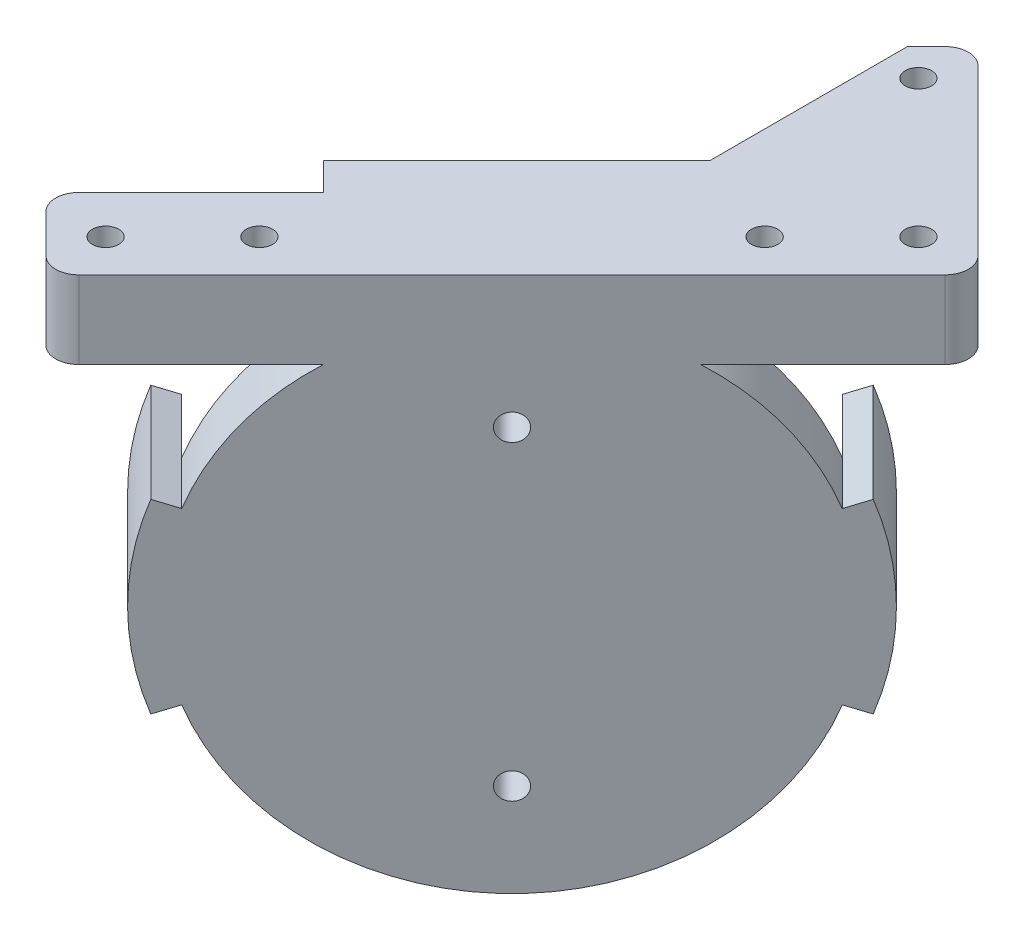
SolidWorks part; units mm, degrees
material "Zoltek Panex 33"
ref_plane "前视基准面" through (0, 0, 0) normal (0, 0, 1) x (1, 0, 0)
ref_plane "上视基准面" through (0, 0, 0) normal (0, 1, 0) x (1, 0, 0)
ref_plane "右视基准面" through (0, 0, 0) normal (1, 0, 0) x (0, 0, -1)
sketch "草图1" plane through (0, 0, 0) normal (0, 1, 0) x (1, 0, 0)
  line L0 (0, 0) -> (0, 75)
  line L1 (0, 0) -> (75, 0)
  line L2 (0, 0) -> (0, -75)
  line L3 (0, 0) -> (-75, 0)
  line L4 (0, 75) -> (15, 75)
  line L5 (0, 75) -> (-15, 75)
  line L6 (75, 0) -> (75, 15)
  line L7 (75, 0) -> (75, -15)
  line L8 (0, -75) -> (15, -75)
  line L9 (0, -75) -> (-15, -75)
  line L10 (-75, 0) -> (-75, -15)
  line L11 (-75, 0) -> (-75, 15)
  line L12 (75, 0) -> (70, 0)
  arc A0 (-75, 15) -> (-15, 75) centre (-75, 75) ccw
  arc A1 (15, 75) -> (75, 15) centre (75, 75) ccw
  arc A2 (75, -15) -> (15, -75) centre (75, -75) ccw
  arc A3 (-15, -75) -> (-75, -15) centre (-75, -75) ccw
  circle A4 centre (-11, 70) radius 1.25
  circle A5 centre (11, 70) radius 1.25
  circle A6 centre (70, -11) radius 1.25
  circle A7 centre (70, 11) radius 1.25
  circle A8 centre (-11, -70) radius 1.25
  circle A9 centre (11, -70) radius 1.25
  circle A10 centre (-70, 11) radius 1.25
  circle A11 centre (-70, -11) radius 1.25
  point P9 (0, 0)
  point P21 (0, 0)
  point P32 (0, 0)
  point P35 (0, 0)
  point P44 (0, 0)
  dimension "D1" = 4
extrude "凸台-拉伸1" add sketch "草图1" along normal blind 3 contours A2 L7 L1 L2 L8 A9 A6 | A3 L9 L2 L3 L10 A11 A8 | A0 L11 L3 L0 L5 A4 A10 | A1 L4 L0 L1 L6 A7 A5 region at (-25.2829, 0, -25.2829) region at (25.2829, 0, -25.2829) region at (25.2829, 0, 25.2829) region at (-25.2829, 0, 25.2829)
sketch "草图2" plane through (0, 0, 0) normal (0, -1, 0) x (1, 0, 0)
  line L0 (0, 0) -> (-32.5736, -32.5736)
  line L1 (0, 0) -> (32.5736, -32.5736)
  line L2 (-31.4663, 0.3536) -> (-0.3536, 31.4663)
  line L3 (31.4663, -0.3536) -> (-0.3536, 31.4663)
  line L4 (0.3536, -31.4663) -> (31.4663, -0.3536)
  line L5 (0.3536, -31.4663) -> (-31.4663, 0.3536)
  arc A0 (-15, -75) -> (-75, -15) centre (-75, -75) ccw construction
  circle A2 centre (0.3536, -31.4663) radius 1.5
  circle A3 centre (31.4663, -0.3536) radius 1.5
  circle A4 centre (-0.3536, 31.4663) radius 1.5
  circle A5 centre (-31.4663, 0.3536) radius 1.5
  point P12 (-15.5563, -15.5563)
  point P16 (-15.9099, 15.9099)
  point P17 (15.9099, -15.9099)
extrude "切除-拉伸1" cut sketch "草图2" against normal blind 3 contours A3 | A2 | A5 | A4
sketch "草图3" plane through (0, 3, 0) normal (0, 1, 0) x (1, 0, 0)
  line L0 (0.3536, 31.4663) -> (-31.4663, -0.3536)
  line L1 (-15.5563, 15.5563) -> (-22.6274, 22.6274)
  line L2 (-15.5563, 15.5563) -> (-12.0208, 19.0919)
  line L3 (-15.5563, 15.5563) -> (-19.0919, 12.0208)
  line L4 (-19.0919, 12.0208) -> (-22.6274, 22.6274)
  line L5 (-12.0208, 19.0919) -> (-22.6274, 22.6274)
extrude "切除-拉伸2" cut sketch "草图3" against normal blind 3 contours L0 L5 L1 | L4 L0 L1 region at (-16.7349, 3, -19.0919) region at (-19.0919, 3, -16.7349)
sketch "草图4" plane through (0, 3, 0) normal (0, 1, 0) x (1, 0, 0)
  line L0 (31.4663, 0.3536) -> (-0.3536, -31.4663)
  line L1 (0, 0) -> (21.2132, -21.2132)
  line L2 (28.2843, -14.1421) -> (14.1421, -28.2843)
  line L3 (14.1421, -28.2843) -> (28.2843, -14.1421) construction
  line L4 (8.4817, -22.6239) -> (22.6239, -8.4817)
  line L5 (19.8025, -33.9447) -> (33.9447, -19.8025)
  arc A0 (8.4817, -22.6239) -> (19.8025, -33.9447) centre (14.1421, -28.2843) ccw
  arc A1 (33.9447, -19.8025) -> (22.6239, -8.4817) centre (28.2843, -14.1421) ccw
  point P9 (21.2132, -21.2132)
extrude "切除-拉伸3" cut sketch "草图4" against normal blind 3 contours L5 A1 L0 A0 region at (21.2143, 3, 21.2143)
sketch "草图5" plane through (0, 3, 0) normal (0, 1, 0) x (1, 0, 0)
  line L0 (-12.0208, 19.0919) -> (-8.4853, 22.6274)
  line L1 (-8.4853, 22.6274) -> (-22.6274, 22.6274)
  line L2 (-19.0919, 12.0208) -> (-22.6274, 8.4853)
  line L3 (-22.6274, 8.4853) -> (-22.6274, 22.6274)
  line L4 (-12.0208, 19.0919) -> (-22.6274, 22.6274)
  line M28 (-19.0919, 12.0208) -> (-22.6274, 22.6274)
extrude "切除-拉伸4" cut sketch "草图5" against normal blind 10 contours L3 L2 M28 | L4 L0 L1 region at (-21.4489, 3, -14.3778)
sketch "草图6" plane through (0, 3, 0) normal (0, 1, 0) x (1, 0, 0)
  line L0 (0, 0) -> (-28.2843, -28.2843)
  line L1 (-28.2843, -28.2843) -> (-35.3553, -21.2132)
  line L2 (0, 0) -> (-22.6274, 22.6274)
  circle A0 centre (-35.3553, -21.2132) radius 1.5
  circle A1 centre (-21.2132, -35.3553) radius 1.5
  circle A2 centre (35.3553, 21.2132) radius 1.5
  circle A3 centre (21.2132, 35.3553) radius 1.5
extrude "切除-拉伸5" cut sketch "草图6" against normal blind 10 contours A1 | A0 | A2 | A3
sketch "草图7" plane through (0, 3, 0) normal (0, 1, 0) x (1, 0, 0)
  circle A0 centre (-29.6985, 29.6985) radius 1.5
  circle A1 centre (29.6985, 29.6985) radius 1.5
  circle A2 centre (29.6985, -29.6985) radius 1.5
  circle A3 centre (-29.6985, -29.6985) radius 1.5
  point P11 (0, 0)
  dimension "D1" = 4
extrude "切除-拉伸8" cut sketch "草图7" against normal blind 10
sketch "草图8" plane through (0, 3, 0) normal (0, 1, 0) x (1, 0, 0)
  circle A0 centre (-11, 55) radius 1.5
  circle A1 centre (11, 55) radius 1.5
  circle A2 centre (55, 11) radius 1.5
  circle A3 centre (55, -11) radius 1.5
  circle A4 centre (11, -55) radius 1.5
  circle A5 centre (-11, -55) radius 1.5
  circle A6 centre (-55, -11) radius 1.5
  circle A7 centre (-55, 11) radius 1.5
  point P21 (0, 0)
  dimension "D1" = 4
extrude "切除-拉伸9" cut sketch "草图8" against normal blind 10
sketch "草图9" plane through (0, 3, 0) normal (0, 1, 0) x (1, 0, 0)
  circle A0 centre (0, 0) radius 15
extrude "切除-拉伸10" cut sketch "草图9" against normal blind 10
sketch "草图11" plane through (0, 3, 0) normal (0, 1, 0) x (1, 0, 0)
  circle A0 centre (-35.3553, -21.2132) radius 1.5
  circle A2 centre (35.3553, 21.2132) radius 1.5
  circle A3 centre (21.2132, 35.3553) radius 1.5
  circle A4 centre (0.3536, 31.4663) radius 1.5
  circle A5 centre (31.4663, 0.3536) radius 1.5
  circle A6 centre (-0.3536, -31.4663) radius 1.5
  circle A7 centre (-31.4663, -0.3536) radius 1.5
  circle A8 centre (-21.2132, -35.3553) radius 1.5
extrude "凸台-拉伸3" add sketch "草图11" against normal blind 3
sketch "草图12" plane through (0, 3, 0) normal (0, 1, 0) x (1, 0, 0)
  line L0 (0, 0) -> (-40, 0)
  line L1 (-40, 0) -> (-40, 10)
  line L2 (-40, 0) -> (-40, -10)
  line L3 (-40, -10) -> (-40, 10) construction
  line L4 (-44, -10) -> (-44, 10)
  line L5 (-36, -10) -> (-36, 10)
  line L6 (-10, 40) -> (10, 40) construction
  line L7 (-10, 44) -> (10, 44)
  line L8 (-10, 36) -> (10, 36)
  line L9 (40, 10) -> (40, -10) construction
  line L10 (44, 10) -> (44, -10)
  line L11 (36, 10) -> (36, -10)
  line L12 (10, -40) -> (-10, -40) construction
  line L13 (10, -44) -> (-10, -44)
  line L14 (10, -36) -> (-10, -36)
  arc A0 (-44, -10) -> (-36, -10) centre (-40, -10) ccw
  arc A1 (-36, 10) -> (-44, 10) centre (-40, 10) ccw
  arc A2 (-10, 44) -> (-10, 36) centre (-10, 40) ccw
  arc A3 (10, 36) -> (10, 44) centre (10, 40) ccw
  arc A4 (44, 10) -> (36, 10) centre (40, 10) ccw
  arc A5 (36, -10) -> (44, -10) centre (40, -10) ccw
  arc A6 (10, -44) -> (10, -36) centre (10, -40) ccw
  arc A7 (-10, -36) -> (-10, -44) centre (-10, -40) ccw
  point P3 (-40, 0)
  point P13 (0, 40)
  point P20 (40, 0)
  point P27 (0, -40)
  point P34 (0, 0)
  dimension "D1" = 4
extrude "切除-拉伸12" cut sketch "草图12" against normal blind 3 contours L5 A1 L4 A0 | L8 A3 L7 A2 | L11 A5 L10 A4 | L14 A7 L13 A6 region at (-43.7088, 3, 0) region at (0, 3, -40) region at (40, 3, 0) region at (0, 3, 40)
sketch "草图14" plane through (0, 3, 0) normal (0, 1, 0) x (1, 0, 0)
  line L0 (22.8277, -8.285) -> (8.285, -22.8277) construction
  line L1 (19.8025, -33.9447) -> (33.9447, -19.8025) construction
  line L2 (8.285, -22.8277) -> (22.8277, -8.285)
  line L3 (22.8277, -8.285) -> (19.8025, -33.9447)
  line L4 (19.8025, -33.9447) -> (33.9447, -19.8025)
  arc A0 (8.285, -22.8277) -> (19.8025, -33.9447) centre (14.1421, -28.2843) ccw
  arc A1 (8.285, -22.8277) -> (19.8025, -33.9447) centre (14.1421, -28.2843) ccw construction
  arc A2 (33.9447, -19.8025) -> (22.8277, -8.285) centre (28.2843, -14.1421) ccw construction
  arc A3 (22.8277, -8.285) -> (32.1857, -7.1522) centre (28.2843, -14.1421) ccw
  circle A4 centre (28.2843, -14.1421) radius 8.005
extrude "凸台-拉伸4" add sketch "草图14" against normal blind 3 contours A3 A4 L3 | L2 A3 L3 | A3 L2 A0 L3 | A3 L3 L4 region at (14.6624, 3, 25.7239) region at (21.4582, 3, 13.3381) region at (24.21, 3, 25.4431) region at (28.7736, 3, 14.1998)
sketch "草图15" plane through (0, 3, 0) normal (0, 1, 0) x (1, 0, 0)
  circle A0 centre (0, 0) radius 15
extrude "凸台-拉伸5" add sketch "草图15" against normal blind 3
sketch "草图17" plane through (0, 3, 0) normal (0, 1, 0) x (1, 0, 0)
  line L0 (0, 0) -> (0, -20)
  line L1 (0, -20) -> (0, -10) construction
  line L2 (-2, -20) -> (-2, -10)
  line L3 (2, -20) -> (2, -10)
  line L4 (-20, 0) -> (-10, 0) construction
  line L5 (-20, 2) -> (-10, 2)
  line L6 (-20, -2) -> (-10, -2)
  line L7 (0, 20) -> (0, 10) construction
  line L8 (2, 20) -> (2, 10)
  line L9 (-2, 20) -> (-2, 10)
  line L10 (20, 0) -> (10, 0) construction
  line L11 (20, -2) -> (10, -2)
  line L12 (20, 2) -> (10, 2)
  arc A0 (-2, -20) -> (2, -20) centre (0, -20) ccw
  arc A1 (2, -10) -> (-2, -10) centre (0, -10) ccw
  arc A2 (-20, 2) -> (-20, -2) centre (-20, 0) ccw
  arc A3 (-10, -2) -> (-10, 2) centre (-10, 0) ccw
  arc A4 (2, 20) -> (-2, 20) centre (0, 20) ccw
  arc A5 (-2, 10) -> (2, 10) centre (0, 10) ccw
  arc A6 (20, -2) -> (20, 2) centre (20, 0) ccw
  arc A7 (10, 2) -> (10, -2) centre (10, 0) ccw
  point P3 (0, -15)
  point P13 (-15, 0)
  point P20 (0, 15)
  point P27 (15, 0)
  point P33 (0, 0)
  dimension "D1" = 4
extrude "切除-拉伸13" cut sketch "草图17" against normal blind 3 contours L8 A5 L9 A4 | L12 A7 L11 A6 | L3 A1 L2 A0 | L5 A3 L6 A2
sketch "草图18" plane through (0, 3, 0) normal (0, 1, 0) x (1, 0, 0)
  line L0 (0, 0) -> (-32.5736, 32.5736)
  line L1 (-32.5736, 32.5736) -> (-46.7157, 46.7157)
  line L2 (-50.2513, 50.2513) -> (-61.9773, 38.5252)
  line L3 (-46.7157, 46.7157) -> (-50.2513, 50.2513)
  line L4 (-61.9773, 38.5252) -> (-38.5252, 61.9773)
  line L5 (-38.5252, 61.9773) -> (-22.5002, 45.9523)
  line L6 (-61.9773, 38.5252) -> (-45.9523, 22.5002)
  arc A0 (-75, 15) -> (-15, 75) centre (-75, 75) ccw construction
  circle A1 centre (-67.9289, 67.9289) radius 30
  circle A2 centre (-75, 75) radius 60
extrude "凸台-拉伸7" add sketch "草图18" against normal blind 3 contours L4 A1 L2 | L2 A1 L3 | L3 A1 L4 | L6 A2 L1 A1 | L1 A2 L5 A1 region at (-46.4984, 3, -34.5306) region at (-34.5306, 3, -46.4984) region at (-53.277, 3, -44.3758) region at (-44.3758, 3, -53.277) region at (-68.7208, 3, -68.7208)
sketch "草图19" plane through (0, 3, 0) normal (0, 1, 0) x (1, 0, 0)
  line L0 (-61.9773, 38.5252) -> (-38.5252, 61.9773)
  line L1 (-50.2513, 50.2513) -> (-36.1091, 36.1091)
  line L2 (-36.1091, 36.1091) -> (-43.1802, 29.0381)
  line L3 (-36.1091, 36.1091) -> (-29.0381, 43.1802)
  line L4 (-29.0381, 43.1802) -> (-37.1408, 51.2829)
  line L5 (-37.1408, 51.2829) -> (-51.2829, 37.1408)
  line L6 (-51.2829, 37.1408) -> (-43.1802, 29.0381)
  circle A1 centre (-67.9289, 67.9289) radius 35
  circle A2 centre (-67.9289, 67.9289) radius 45
extrude "切除-拉伸14" cut sketch "草图19" against normal blind 3 contours L1 A2 L4 A1 | L6 A2 L1 A1 region at (-36.3949, 3, -43.5045) region at (-43.5045, 3, -36.3949)
sketch "草图21" plane through (0, 3, 0) normal (0, 1, 0) x (1, 0, 0)
  line L0 (-61.9773, 38.5252) -> (-38.5252, 61.9773)
  line L1 (-67.9289, 67.9289) -> (-53.7868, 53.7868)
  line L2 (-82.0711, 82.0711) -> (-75, 75)
  line L3 (-67.9289, 67.9289) -> (-82.0711, 82.0711)
  line L4 (-53.7868, 53.7868) -> (-60.8579, 60.8579)
  line L5 (-82.0711, 82.0711) -> (-75, 75) construction
  line L6 (-81.1872, 82.955) -> (-74.1161, 75.8839)
  line L7 (-82.955, 81.1872) -> (-75.8839, 74.1161)
  line L8 (-60.8579, 60.8579) -> (-53.7868, 53.7868) construction
  line L9 (-59.974, 61.7417) -> (-52.9029, 54.6707)
  line L10 (-61.7417, 59.974) -> (-54.6707, 52.9029)
  arc A0 (-81.1872, 82.955) -> (-82.955, 81.1872) centre (-82.0711, 82.0711) ccw
  arc A1 (-75.8839, 74.1161) -> (-74.1161, 75.8839) centre (-75, 75) ccw
  arc A2 (-59.974, 61.7417) -> (-61.7417, 59.974) centre (-60.8579, 60.8579) ccw
  arc A3 (-54.6707, 52.9029) -> (-52.9029, 54.6707) centre (-53.7868, 53.7868) ccw
  point P2 (-78.5355, 78.5355)
  point P15 (-57.3223, 57.3223)
extrude "切除-拉伸15" cut sketch "草图21" against normal blind 3 contours A1 L6 A0 L7 | A3 L9 A2 L10 region at (-75, 3, -73.8854)
pattern_circular "阵列(圆周)1" count 8 over 360 about axis through (-67.9289, 3, -67.9289) along (0, 1, 0) of "切除-拉伸15"
sketch "草图22" plane through (0, 3, 0) normal (0, 1, 0) x (1, 0, 0)
  line L0 (0, 0) -> (9.8995, 9.8995)
  line L1 (0, 0) -> (-9.8995, -9.8995)
  circle A0 centre (9.8995, 9.8995) radius 1.25
  circle A1 centre (-9.8995, -9.8995) radius 1.25
extrude "切除-拉伸17" cut sketch "草图22" against normal blind 3 contours A0 | A1
sketch "草图23" plane through (0, 3, 0) normal (0, 1, 0) x (1, 0, 0)
  circle A0 centre (0, 30) radius 1.5
  circle A1 centre (30, 0) radius 1.5
  circle A2 centre (0, -30) radius 1.5
  circle A3 centre (-30, 0) radius 1.5
  point P13 (0, 0)
  dimension "D1" = 4
extrude "切除-拉伸18" cut sketch "草图23" against normal blind 10
sketch "草图24" plane through (0, 3, 0) normal (0, 1, 0) x (1, 0, 0)
  circle A0 centre (-15, -15) radius 1.5
  circle A1 centre (15, 15) radius 1.5
extrude "切除-拉伸19" cut sketch "草图24" against normal blind 10
sketch "草图25" plane through (0, 3, 0) normal (0, 1, 0) x (1, 0, 0)
  circle A0 centre (-75, 75) radius 60
extrude "切除-拉伸20" cut sketch "草图25" against normal blind 10
sketch "草图26" plane through (0, 3, 0) normal (0, 1, 0) x (1, 0, 0)
  line L0 (-15, 75) -> (-75, 15)
  circle A0 centre (-75, 75) radius 60
extrude "凸台-拉伸8" add sketch "草图26" against normal blind 3 contours L0 A0 region at (-39.9612, 3, -39.9612)
sketch "草图27" plane through (0, 0, 0) normal (0, -1, 0) x (1, 0, 0)
  line L0 (-45, -45) -> (-23.5998, -66.4002)
  line L1 (-15, -75) -> (-75, -15) construction
  line L2 (-23.5998, -66.4002) -> (-66.0262, -23.9738)
  line L3 (-15, -75) -> (-22.0711, -82.0711)
  line L4 (-22.0711, -82.0711) -> (-75, -15)
  line L5 (-75, -15) -> (-82.0711, -22.0711)
  line L6 (-82.0711, -22.0711) -> (-22.0711, -82.0711)
  line L7 (75, 15) -> (15, 75)
  line L8 (15, 75) -> (22.0711, 82.0711)
  line L9 (75, 15) -> (82.0711, 22.0711)
  line L10 (82.0711, 22.0711) -> (22.0711, 82.0711)
  line L11 (-15, -75) -> (-75, -15)
  line L12 (-22.0711, -82.0711) -> (-29.1421, -89.1421)
  line L13 (-29.1421, -89.1421) -> (-82.0711, -22.0711)
  line L14 (-82.0711, -22.0711) -> (-89.1421, -29.1421)
  line L15 (-89.1421, -29.1421) -> (-29.1421, -89.1421)
  circle A0 centre (75, 75) radius 60
extrude "凸台-拉伸10" add sketch "草图27" against normal blind 3 contours L14 L15 L13 | L13 L12 L6 | L5 L6 L4 | L3 L11 L0 L2 L4 region at (-37.357, 0, -57.357) region at (-59.714, 0, -39.714) region at (-44.4281, 0, -64.4281) region at (-66.7851, 0, -46.7851)
sketch "草图28" plane through (0, 0, 0) normal (0, -1, 0) x (1, 0, 0)
  line L0 (-59.1421, -59.1421) -> (-52.0711, -52.0711)
  line L1 (-89.1421, -29.1421) -> (-29.1421, -89.1421) construction
  line L2 (-52.0711, -52.0711) -> (-25.9081, -78.234)
  line L3 (-52.0711, -52.0711) -> (-78.234, -25.9081)
  line L4 (11, -70) -> (8.198, -68.4493)
  circle A1 centre (11, -70) radius 1.5
  circle A2 centre (-11, -70) radius 1.5
  circle A3 centre (-70, -11) radius 1.5
  circle A4 centre (-70, 11) radius 1.5
  circle A5 centre (-11, 70) radius 1.5
  circle A6 centre (11, 70) radius 1.5
  circle A7 centre (70, 11) radius 1.5
  circle A8 centre (70, -11) radius 1.5
  circle A9 centre (-25.9081, -78.234) radius 1.54
  circle A10 centre (-78.234, -25.9081) radius 1.52
extrude "切除-拉伸21" cut sketch "草图28" against normal blind 3 contours A9 | A10 | A3 | A4 | A2 | A1 | A8 | A7 | A5 | A6 region at (-25.3355, 0, -76.8515) region at (-79.5986, 0, -25.3429)
sketch "草图29" plane through (0, 0, 0) normal (0, -1, 0) x (1, 0, 0)
  line L0 (-59.1421, -59.1421) -> (-22.6274, -22.6274)
  line L1 (-78.234, -25.9081) -> (-68.3345, -35.8076)
  line L2 (-89.1421, -29.1421) -> (-29.1421, -89.1421) construction
  circle A0 centre (-68.3345, -35.8076) radius 1.5
  circle A1 centre (-35.8076, -68.3345) radius 1.5
extrude "切除-拉伸22" cut sketch "草图29" against normal blind 3 contours A1 | A0
sketch "草图30" plane through (0, 0, 0) normal (0, -1, 0) x (1, 0, 0)
  line L0 (-29.1421, -89.1421) -> (-89.1421, -29.1421)
  line L1 (-29.1421, -89.1421) -> (-43.2843, -103.2843)
  line L2 (-89.1421, -29.1421) -> (-103.2843, -43.2843)
  line L3 (-43.2843, -103.2843) -> (-103.2843, -43.2843)
extrude "凸台-拉伸11" add sketch "草图30" against normal blind 3
sketch "草图31" plane through (0, 0, 0) normal (0, -1, 0) x (1, 0, 0)
  line L1 (-25.9081, -78.234) -> (-78.234, -25.9081)
  circle A0 centre (-43.5858, -95.9117) radius 1.5
  circle A1 centre (-53.4853, -86.0122) radius 1.5
  circle A2 centre (-86.0122, -53.4853) radius 1.5
  circle A3 centre (-95.9117, -43.5858) radius 1.5
extrude "切除-拉伸23" cut sketch "草图31" against normal blind 3 contours A0 | A1 | A2 | A3
sketch "草图32" plane through (0, 0, 0) normal (0, -1, 0) x (1, 0, 0)
  line L0 (75, 15) -> (15, 75)
  line L1 (75, 15) -> (15, 75)
  line L2 (75, 15) -> (89.1421, 29.1421)
  line L3 (15, 75) -> (29.1421, 89.1421)
  line L4 (89.1421, 29.1421) -> (29.1421, 89.1421)
  circle A0 centre (75, 75) radius 60
extrude "凸台-拉伸12" add sketch "草图32" against normal blind 3 contours L0 A0 | L2 L4 L3 L0 region at (39.9612, 0, 39.9612) region at (52.0711, 0, 52.0711)
sketch "草图33" plane through (0, 0, 0) normal (0, -1, 0) x (-1, 0, 0)
  line L0 (-29.6985, -29.6985) -> (-59.1421, -59.1421)
  line L1 (-89.1421, -29.1421) -> (-29.1421, -89.1421) construction
  line L2 (-44.4203, -44.4203) -> (-14.6894, -44.4203)
  line L3 (-14.6894, -44.4203) -> (-44.4203, -16.8394)
  line L4 (-44.4203, -16.8394) -> (-44.4203, -44.4203)
  line L5 (-29.5549, -44.4203) -> (-19.5549, -44.4203) construction
  line L6 (-29.5549, -42.92) -> (-19.5549, -42.92)
  line L7 (-29.5549, -45.9207) -> (-19.5549, -45.9207)
  line L8 (-44.4203, -59.2858) -> (-44.4203, -69.2858) construction
  line L9 (-42.92, -59.2858) -> (-42.92, -69.2858)
  line L10 (-45.9207, -59.2858) -> (-45.9207, -69.2858)
  line L11 (-59.2858, -44.4203) -> (-69.2858, -44.4203) construction
  line L12 (-59.2858, -45.9207) -> (-69.2858, -45.9207)
  line L13 (-59.2858, -42.92) -> (-69.2858, -42.92)
  line L14 (-44.4203, -29.5549) -> (-44.4203, -19.5549) construction
  line L15 (-45.9207, -29.5549) -> (-45.9207, -19.5549)
  line L16 (-42.92, -29.5549) -> (-42.92, -19.5549)
  arc A0 (-29.5549, -42.92) -> (-29.5549, -45.9207) centre (-29.5549, -44.4203) ccw
  arc A1 (-19.5549, -45.9207) -> (-19.5549, -42.92) centre (-19.5549, -44.4203) ccw
  arc A2 (-42.92, -59.2858) -> (-45.9207, -59.2858) centre (-44.4203, -59.2858) ccw
  arc A3 (-45.9207, -69.2858) -> (-42.92, -69.2858) centre (-44.4203, -69.2858) ccw
  arc A4 (-59.2858, -45.9207) -> (-59.2858, -42.92) centre (-59.2858, -44.4203) ccw
  arc A5 (-69.2858, -42.92) -> (-69.2858, -45.9207) centre (-69.2858, -44.4203) ccw
  arc A6 (-45.9207, -29.5549) -> (-42.92, -29.5549) centre (-44.4203, -29.5549) ccw
  arc A7 (-42.92, -19.5549) -> (-45.9207, -19.5549) centre (-44.4203, -19.5549) ccw
  point P10 (-24.5549, -44.4203)
  point P20 (-44.4203, -64.2858)
  point P27 (-64.2858, -44.4203)
  point P34 (-44.4203, -24.5549)
  point P39 (-44.4203, -44.4203)
  dimension "D1" = 4
extrude "切除-拉伸24" cut sketch "草图33" against normal blind 3 contours L10 A3 L9 A2 | L7 A1 L6 A0 | L12 A5 L13 A4 | L15 A7 L16 A6
sketch "草图34" plane through (0, 0, 0) normal (0, -1, 0) x (1, 0, 0)
  line L0 (29.1421, 89.1421) -> (89.1421, 29.1421)
  line L1 (29.1421, 89.1421) -> (43.2843, 103.2843)
  line L2 (89.1421, 29.1421) -> (103.2843, 43.2843)
  line L3 (43.2843, 103.2843) -> (103.2843, 43.2843)
  line L4 (75, 15) -> (89.1421, 29.1421) construction
  line L5 (89.1421, 29.1421) -> (29.1421, 89.1421) construction
extrude "凸台-拉伸13" add sketch "草图34" against normal blind 3
sketch "草图35" plane through (0, 0, 0) normal (0, -1, 0) x (1, 0, 0)
  line L0 (10, 40) -> (15.6569, 34.3431)
  line L1 (10, 40) -> (15.6569, 34.3431) construction
  line L2 (12.8284, 42.8284) -> (18.4853, 37.1716)
  line L3 (7.1716, 37.1716) -> (12.8284, 31.5147)
  line L4 (-10, 40) -> (-15.6569, 34.3431) construction
  line L5 (-7.1716, 37.1716) -> (-12.8284, 31.5147)
  line L6 (-12.8284, 42.8284) -> (-18.4853, 37.1716)
  line L7 (40, -10) -> (34.3431, -15.6569) construction
  line L8 (42.8284, -12.8284) -> (37.1716, -18.4853)
  line L9 (37.1716, -7.1716) -> (31.5147, -12.8284)
  line L10 (40, 10) -> (34.3431, 15.6569) construction
  line L11 (37.1716, 7.1716) -> (31.5147, 12.8284)
  line L12 (42.8284, 12.8284) -> (37.1716, 18.4853)
  line L13 (-10, -40) -> (-15.6569, -34.3431) construction
  line L14 (-12.8284, -42.8284) -> (-18.4853, -37.1716)
  line L15 (-7.1716, -37.1716) -> (-12.8284, -31.5147)
  line L16 (10, -40) -> (15.6569, -34.3431) construction
  line L17 (7.1716, -37.1716) -> (12.8284, -31.5147)
  line L18 (12.8284, -42.8284) -> (18.4853, -37.1716)
  line L19 (-40, 10) -> (-34.3431, 15.6569) construction
  line L20 (-42.8284, 12.8284) -> (-37.1716, 18.4853)
  line L21 (-37.1716, 7.1716) -> (-31.5147, 12.8284)
  line L22 (-40, -10) -> (-34.3431, -15.6569) construction
  line L23 (-37.1716, -7.1716) -> (-31.5147, -12.8284)
  line L24 (-42.8284, -12.8284) -> (-37.1716, -18.4853)
  arc A0 (12.8284, 42.8284) -> (7.1716, 37.1716) centre (10, 40) ccw
  arc A1 (12.8284, 31.5147) -> (18.4853, 37.1716) centre (15.6569, 34.3431) ccw
  arc A2 (-7.1716, 37.1716) -> (-12.8284, 42.8284) centre (-10, 40) ccw
  arc A3 (-18.4853, 37.1716) -> (-12.8284, 31.5147) centre (-15.6569, 34.3431) ccw
  arc A4 (42.8284, -12.8284) -> (37.1716, -7.1716) centre (40, -10) ccw
  arc A5 (31.5147, -12.8284) -> (37.1716, -18.4853) centre (34.3431, -15.6569) ccw
  arc A6 (37.1716, 7.1716) -> (42.8284, 12.8284) centre (40, 10) ccw
  arc A7 (37.1716, 18.4853) -> (31.5147, 12.8284) centre (34.3431, 15.6569) ccw
  arc A8 (-12.8284, -42.8284) -> (-7.1716, -37.1716) centre (-10, -40) ccw
  arc A9 (-12.8284, -31.5147) -> (-18.4853, -37.1716) centre (-15.6569, -34.3431) ccw
  arc A10 (7.1716, -37.1716) -> (12.8284, -42.8284) centre (10, -40) ccw
  arc A11 (18.4853, -37.1716) -> (12.8284, -31.5147) centre (15.6569, -34.3431) ccw
  arc A12 (-42.8284, 12.8284) -> (-37.1716, 7.1716) centre (-40, 10) ccw
  arc A13 (-31.5147, 12.8284) -> (-37.1716, 18.4853) centre (-34.3431, 15.6569) ccw
  arc A14 (-37.1716, -7.1716) -> (-42.8284, -12.8284) centre (-40, -10) ccw
  arc A15 (-37.1716, -18.4853) -> (-31.5147, -12.8284) centre (-34.3431, -15.6569) ccw
  point P3 (12.8284, 37.1716)
  point P11 (-12.8284, 37.1716)
  point P21 (37.1716, -12.8284)
  point P28 (37.1716, 12.8284)
  point P35 (-12.8284, -37.1716)
  point P42 (12.8284, -37.1716)
  point P49 (-37.1716, 12.8284)
  point P56 (-37.1716, -12.8284)
  point P61 (0, 0)
  dimension "D1" = 4
extrude "切除-拉伸25" cut sketch "草图35" against normal blind 10 contours L12 A7 L11 A6 | L3 A1 L2 A0 | L6 A3 L5 A2 | L21 A13 L20 A12 | L24 A15 L23 A14 | L15 A9 L14 A8 | L18 A11 L17 A10 | L9 A5 L8 A4 region at (15.5203, 0, 39.8634) region at (-12.8284, 0, 37.1716) region at (37.1716, 0, -12.8284) region at (37.1716, 0, 12.8284) region at (-12.8284, 0, -37.1716) region at (12.8284, 0, -37.1716) region at (-37.1716, 0, 12.8284) region at (-37.1716, 0, -12.8284)
sketch "草图36" plane through (0, 0, 0) normal (0, -1, 0) x (1, 0, 0)
  line L0 (19.5549, 44.4203) -> (29.5549, 44.4203) construction
  line L1 (19.5549, 45.9203) -> (29.5549, 45.9203)
  line L2 (19.5549, 42.9203) -> (29.5549, 42.9203)
  line L3 (26.6259, 51.4914) -> (36.6259, 51.4914) construction
  line L4 (44.4203, 69.2858) -> (44.4203, 59.2858) construction
  line L5 (45.9203, 69.2858) -> (45.9203, 59.2858)
  line L6 (42.9203, 69.2858) -> (42.9203, 59.2858)
  line L7 (69.2858, 44.4203) -> (59.2858, 44.4203) construction
  line L8 (69.2858, 42.9203) -> (59.2858, 42.9203)
  line L9 (69.2858, 45.9203) -> (59.2858, 45.9203)
  line L10 (44.4203, 19.5549) -> (44.4203, 29.5549) construction
  line L11 (42.9203, 19.5549) -> (42.9203, 29.5549)
  line L12 (45.9203, 19.5549) -> (45.9203, 29.5549)
  line L13 (26.6259, 52.9914) -> (36.6259, 52.9914)
  line L14 (26.6259, 49.9914) -> (36.6259, 49.9914)
  line L15 (51.4914, 76.3568) -> (51.4914, 66.3568) construction
  line L16 (52.9914, 76.3568) -> (52.9914, 66.3568)
  line L17 (49.9914, 76.3568) -> (49.9914, 66.3568)
  line L18 (76.3568, 51.4914) -> (66.3568, 51.4914) construction
  line L19 (76.3568, 49.9914) -> (66.3568, 49.9914)
  line L20 (76.3568, 52.9914) -> (66.3568, 52.9914)
  line L21 (51.4914, 26.6259) -> (51.4914, 36.6259) construction
  line L22 (49.9914, 26.6259) -> (49.9914, 36.6259)
  line L23 (52.9914, 26.6259) -> (52.9914, 36.6259)
  arc A0 (19.5549, 45.9203) -> (19.5549, 42.9203) centre (19.5549, 44.4203) ccw
  arc A1 (29.5549, 42.9203) -> (29.5549, 45.9203) centre (29.5549, 44.4203) ccw
  arc A2 (45.9203, 69.2858) -> (42.9203, 69.2858) centre (44.4203, 69.2858) ccw
  arc A3 (42.9203, 59.2858) -> (45.9203, 59.2858) centre (44.4203, 59.2858) ccw
  arc A4 (69.2858, 42.9203) -> (69.2858, 45.9203) centre (69.2858, 44.4203) ccw
  arc A5 (59.2858, 45.9203) -> (59.2858, 42.9203) centre (59.2858, 44.4203) ccw
  arc A6 (42.9203, 19.5549) -> (45.9203, 19.5549) centre (44.4203, 19.5549) ccw
  arc A7 (45.9203, 29.5549) -> (42.9203, 29.5549) centre (44.4203, 29.5549) ccw
  arc A8 (26.6259, 52.9914) -> (26.6259, 49.9914) centre (26.6259, 51.4914) ccw
  arc A9 (36.6259, 49.9914) -> (36.6259, 52.9914) centre (36.6259, 51.4914) ccw
  arc A10 (52.9914, 76.3568) -> (49.9914, 76.3568) centre (51.4914, 76.3568) ccw
  arc A11 (49.9914, 66.3568) -> (52.9914, 66.3568) centre (51.4914, 66.3568) ccw
  arc A12 (76.3568, 49.9914) -> (76.3568, 52.9914) centre (76.3568, 51.4914) ccw
  arc A13 (66.3568, 52.9914) -> (66.3568, 49.9914) centre (66.3568, 51.4914) ccw
  arc A14 (49.9914, 26.6259) -> (52.9914, 26.6259) centre (51.4914, 26.6259) ccw
  arc A15 (52.9914, 36.6259) -> (49.9914, 36.6259) centre (51.4914, 36.6259) ccw
  point P4 (24.5549, 44.4203)
  point P13 (31.6259, 51.4914)
  point P19 (44.4203, 64.2858)
  point P26 (64.2858, 44.4203)
  point P33 (44.4203, 24.5549)
  point P41 (51.4914, 71.3568)
  point P48 (71.3568, 51.4914)
  point P55 (51.4914, 31.6259)
  dimension "D1" = 2
extrude "切除-拉伸26" cut sketch "草图36" against normal blind 10
sketch "草图37" plane through (0, 0, 0) normal (0, -1, 0) x (1, 0, 0)
  line L0 (44.4203, 69.2858) -> (44.4203, 59.8535) construction
  line L1 (47.888, 69.2858) -> (47.888, 59.8535)
  line L2 (40.9527, 69.2858) -> (40.9527, 59.8535)
  line L3 (60.035, 44.7696) -> (68.5031, 44.7696) construction
  line L4 (60.035, 48.1814) -> (68.5031, 48.1814)
  line L5 (60.035, 41.3579) -> (68.5031, 41.3579)
  line L6 (44.4203, 29.5549) -> (44.4203, 19.6289) construction
  line L7 (48.5122, 29.5549) -> (48.5122, 19.6289)
  line L8 (40.3284, 29.5549) -> (40.3284, 19.6289)
  line L9 (20.3241, 44.7696) -> (29.5195, 44.7696) construction
  line L10 (20.3241, 48.0853) -> (29.5195, 48.0853)
  line L11 (20.3241, 41.454) -> (29.5195, 41.454)
  arc A0 (47.888, 69.2858) -> (40.9527, 69.2858) centre (44.4203, 69.2858) ccw
  arc A1 (40.9527, 59.8535) -> (47.888, 59.8535) centre (44.4203, 59.8535) ccw
  arc A2 (60.035, 48.1814) -> (60.035, 41.3579) centre (60.035, 44.7696) ccw
  arc A3 (68.5031, 41.3579) -> (68.5031, 48.1814) centre (68.5031, 44.7696) ccw
  arc A4 (48.5122, 29.5549) -> (40.3284, 29.5549) centre (44.4203, 29.5549) ccw
  arc A5 (40.3284, 19.6289) -> (48.5122, 19.6289) centre (44.4203, 19.6289) ccw
  arc A6 (20.3241, 48.0853) -> (20.3241, 41.454) centre (20.3241, 44.7696) ccw
  arc A7 (29.5195, 41.454) -> (29.5195, 48.0853) centre (29.5195, 44.7696) ccw
  point P3 (44.4203, 64.5696)
  point P8 (64.2691, 44.7696)
  point P15 (44.4203, 24.5919)
  point P23 (24.9218, 44.7696)
extrude "凸台-拉伸14" add sketch "草图37" against normal blind 3
sketch "草图38" plane through (0, 0, 0) normal (0, -1, 0) x (1, 0, 0)
  line L0 (-52.4533, -52.4533) -> (-53.8675, -51.0391)
  line L1 (-51.0391, -53.8675) -> (-52.4533, -52.4533)
  line L2 (57.1482, 57.1482) -> (55.734, 58.5624)
  line L3 (-53.8675, -51.0391) -> (-51.0391, -51.0391)
  line L4 (-51.0391, -53.8675) -> (-51.0391, -51.0391)
  line L5 (58.5624, 55.734) -> (57.1482, 57.1482)
  line L6 (55.734, 58.5624) -> (58.5624, 58.5624)
  line L7 (58.5624, 55.734) -> (58.5624, 58.5624)
  line L8 (59.4914, 53.4914) -> (61.4914, 51.4914)
  line L9 (59.4914, 49.4914) -> (61.4914, 51.4914)
  line L10 (59.4914, 49.4914) -> (59.4914, 51.4914)
  line L11 (59.4914, 51.4914) -> (59.4914, 53.4914)
  line L12 (58.5624, 47.2487) -> (58.5624, 44.4203)
  line L13 (55.734, 44.4203) -> (58.5624, 44.4203)
  line L14 (55.734, 44.4203) -> (57.1482, 45.8345)
  line L15 (57.1482, 45.8345) -> (58.5624, 47.2487)
  line L16 (53.4914, 43.4914) -> (51.4914, 41.4914)
  line L17 (49.4914, 43.4914) -> (51.4914, 41.4914)
  line L18 (49.4914, 43.4914) -> (51.4914, 43.4914)
  line L19 (51.4914, 43.4914) -> (53.4914, 43.4914)
  line L20 (47.2487, 44.4203) -> (44.4203, 44.4203)
  line L21 (44.4203, 47.2487) -> (44.4203, 44.4203)
  line L22 (44.4203, 47.2487) -> (45.8345, 45.8345)
  line L23 (45.8345, 45.8345) -> (47.2487, 44.4203)
  line L24 (43.4914, 49.4914) -> (41.4914, 51.4914)
  line L25 (43.4914, 53.4914) -> (41.4914, 51.4914)
  line L26 (43.4914, 53.4914) -> (43.4914, 51.4914)
  line L27 (43.4914, 51.4914) -> (43.4914, 49.4914)
  line L28 (44.4203, 55.734) -> (44.4203, 58.5624)
  line L29 (47.2487, 58.5624) -> (44.4203, 58.5624)
  line L30 (47.2487, 58.5624) -> (45.8345, 57.1482)
  line L31 (45.8345, 57.1482) -> (44.4203, 55.734)
  line L32 (49.4914, 59.4914) -> (51.4914, 61.4914)
  line L33 (53.4914, 59.4914) -> (51.4914, 61.4914)
  line L34 (53.4914, 59.4914) -> (51.4914, 59.4914)
  line L35 (51.4914, 59.4914) -> (49.4914, 59.4914)
  line L36 (-50.1102, -56.1102) -> (-48.1102, -58.1102)
  line L37 (-50.1102, -60.1102) -> (-48.1102, -58.1102)
  line L38 (-50.1102, -60.1102) -> (-50.1102, -58.1102)
  line L39 (-50.1102, -58.1102) -> (-50.1102, -56.1102)
  line L40 (-51.0391, -62.3528) -> (-51.0391, -65.1812)
  line L41 (-53.8675, -65.1812) -> (-51.0391, -65.1812)
  line L42 (-53.8675, -65.1812) -> (-52.4533, -63.767)
  line L43 (-52.4533, -63.767) -> (-51.0391, -62.3528)
  line L44 (-56.1102, -66.1102) -> (-58.1102, -68.1102)
  line L45 (-60.1102, -66.1102) -> (-58.1102, -68.1102)
  line L46 (-60.1102, -66.1102) -> (-58.1102, -66.1102)
  line L47 (-58.1102, -66.1102) -> (-56.1102, -66.1102)
  line L48 (-62.3528, -65.1812) -> (-65.1812, -65.1812)
  line L49 (-65.1812, -62.3528) -> (-65.1812, -65.1812)
  line L50 (-65.1812, -62.3528) -> (-63.767, -63.767)
  line L51 (-63.767, -63.767) -> (-62.3528, -65.1812)
  line L52 (-66.1102, -60.1102) -> (-68.1102, -58.1102)
  line L53 (-66.1102, -56.1102) -> (-68.1102, -58.1102)
  line L54 (-66.1102, -56.1102) -> (-66.1102, -58.1102)
  line L55 (-66.1102, -58.1102) -> (-66.1102, -60.1102)
  line L56 (-65.1812, -53.8675) -> (-65.1812, -51.0391)
  line L57 (-62.3528, -51.0391) -> (-65.1812, -51.0391)
  line L58 (-62.3528, -51.0391) -> (-63.767, -52.4533)
  line L59 (-63.767, -52.4533) -> (-65.1812, -53.8675)
  line L60 (-60.1102, -50.1102) -> (-58.1102, -48.1102)
  line L61 (-56.1102, -50.1102) -> (-58.1102, -48.1102)
  line L62 (-56.1102, -50.1102) -> (-58.1102, -50.1102)
  line L63 (-58.1102, -50.1102) -> (-60.1102, -50.1102)
  circle A0 centre (51.4914, 51.4914) radius 6
  circle A1 centre (-58.1102, -58.1102) radius 6
  point P40 (51.4914, 51.4914)
  point P70 (-58.1102, -58.1102)
  dimension "D1" = 2
extrude "切除-拉伸28" cut sketch "草图38" against normal blind 3
sketch "草图39" plane through (0, 0, 0) normal (0, -1, 0) x (1, 0, 0)
  circle A0 centre (-69.7487, -69.7487) radius 1.5
  circle A1 centre (-73.9914, -65.5061) radius 1.5
  circle A2 centre (-78.234, -61.2635) radius 1.5
  circle A3 centre (-82.4767, -57.0208) radius 1.5
  circle A4 centre (-65.5061, -73.9914) radius 1.5
  circle A5 centre (-61.2635, -78.234) radius 1.5
  circle A6 centre (-57.0208, -82.4767) radius 1.5
extrude "切除-拉伸29" cut sketch "草图39" against normal blind 3
sketch "草图40" plane through (0, 0, 0) normal (0, -1, 0) x (1, 0, 0)
  line L0 (-103.2843, -43.2843) -> (-75, -15)
  line L1 (-103.2843, -43.2843) -> (-43.3385, -103.2301)
  line L2 (-75, -15) -> (-15.0542, -74.9458)
  line L3 (-43.3385, -103.2301) -> (-15.0542, -74.9458)
  line L4 (-75, -15) -> (-103.2843, -43.2843) construction
  line L5 (-75, -15) -> (-100.1459, 10.1459)
  line L6 (-75, -15) -> (50.5274, 110.5274)
  line L7 (-100.1459, 10.1459) -> (25.3815, 135.6732)
  line L8 (50.5274, 110.5274) -> (25.3815, 135.6732)
  line L9 (50.5274, 110.5274) -> (-75, -15)
  line L10 (50.5274, 110.5274) -> (151.7064, 9.3483)
  line L11 (-75, -15) -> (26.179, -116.179)
  line L12 (151.7064, 9.3483) -> (26.179, -116.179)
extrude "切除-拉伸30" cut sketch "草图40" against normal blind 10 contours L12 L10 L6 L2 L11 | L6 L8 L7 L5 region at (38.3532, 0, -2.8258) region at (-24.8093, 0, 60.3366)
sketch "草图41" plane through (0, 0, 0) normal (0, -1, 0) x (-1, 0, 0)
  line L0 (101.163, 41.163) -> (79.9497, 19.9497)
  line L1 (75, 15) -> (103.2843, 43.2843) construction
  line L2 (75.7071, 19.9497) -> (19.9497, 75.7071)
  line L3 (15, 75) -> (43.2843, 103.2843) construction
  line L4 (19.9497, 79.9497) -> (41.163, 101.163)
  line L5 (45.4056, 101.163) -> (47.8284, 98.7401)
  line L6 (103.2843, 43.2843) -> (43.2843, 103.2843) construction
  line L7 (47.8284, 98.7401) -> (47.8284, 73.2843)
  line L8 (73.2843, 47.8284) -> (98.7401, 47.8284)
  line L9 (98.7401, 47.8284) -> (101.163, 45.4056)
  line L10 (47.8284, 73.2843) -> (73.2843, 47.8284)
  arc A0 (41.163, 101.163) -> (45.4056, 101.163) centre (43.2843, 99.0416) cw
  arc A1 (101.163, 41.163) -> (101.163, 45.4056) centre (99.0416, 43.2843) ccw
  arc A2 (79.9497, 19.9497) -> (75.7071, 19.9497) centre (77.8284, 22.0711) cw
  arc A3 (19.9497, 75.7071) -> (19.9497, 79.9497) centre (22.0711, 77.8284) cw
  circle A4 centre (68.3345, 35.8076) radius 1.7
  circle A5 centre (78.234, 25.9081) radius 1.7
  circle A6 centre (95.9117, 43.5858) radius 1.7
  circle A7 centre (43.5858, 95.9117) radius 1.7
  circle A8 centre (25.9081, 78.234) radius 1.7
  circle A9 centre (35.8076, 68.3345) radius 1.7
  point P19 (43.2843, 103.2843)
  point P22 (103.2843, 43.2843)
  point P25 (77.8284, 17.8284)
  point P28 (17.8284, 77.8284)
  dimension "D1" = 3
extrude "凸台-拉伸15" add sketch "草图41" along normal blind 10
sketch "草图42" plane through (-73.2843, 0, -73.2843) normal (-0.7071, 0, -0.7071) x (-0.7071, 0, 0.7071)
  line L0 (42.4264, 0) -> (-42.4264, 0)
  line L1 (42.4264, 0) -> (42.4264, 3)
  line L2 (-42.4264, 0) -> (-42.4264, 3)
  line L3 (42.4264, 3) -> (-42.4264, 3)
extrude "切除-拉伸31" cut sketch "草图42" against normal blind 48
sketch "草图44" plane through (-60.5563, 0, -60.5563) normal (-0.7071, 0, -0.7071) x (-0.7071, 0, 0.7071)
  line L0 (0, -10) -> (0, -5)
  line L1 (18, -10) -> (-18, -10) construction
  line L2 (0, -10) -> (0, -37)
  circle A0 centre (0, -37) radius 32
  line M3 (-18, -10) -> (18, -10)
extrude "切除-拉伸33" cut sketch "草图44" against normal blind 10 contours L0 A0 M3 | A0 L0 M3 region at (-55.9505, -7.986, -65.1622) region at (-65.1622, -7.986, -55.9505)
sketch "草图45" plane through (-53.4853, 0, -53.4853) normal (-0.7071, 0, -0.7071) x (-0.7071, 0, 0.7071)
  line L0 (-30.0702, -47.9446) -> (-32.8892, -48.9707)
  line L1 (30.0702, -47.9446) -> (32.8892, -48.9707)
  line L2 (-30.0702, -26.0554) -> (-32.8892, -25.0293)
  line L3 (-32.8892, -25.0293) -> (-30.0702, -26.0554)
  line L4 (30.0702, -26.0554) -> (32.8892, -25.0293)
  line L5 (32.8892, -25.0293) -> (30.0702, -26.0554)
  arc A0 (-30.0702, -47.9446) -> (30.0702, -47.9446) centre (0, -37) ccw
  circle A1 centre (0, -57) radius 1.7
  circle A2 centre (0, -17) radius 1.7
  arc A3 (32.8892, -48.9707) -> (32.8892, -25.0293) centre (0, -37) ccw
  arc A4 (-32.8892, -25.0293) -> (-32.8892, -48.9707) centre (0, -37) ccw
  arc A5 (30.0702, -26.0554) -> (-30.0702, -26.0554) centre (0, -37) ccw
  line M3 (-17.1756, -10) -> (17.1756, -10)
extrude "凸台-拉伸16" add sketch "草图45" against normal blind 8 contours L4 A5 L2 A4 L0 A0 L1 A3 A1 A2 M3 region at (-53.4853, -38.0481, -53.4853)
sketch "草图46" plane through (0, -10, 0) normal (0, -1, 0) x (1, 0, 0)
  line L0 (-69.1658, -44.8759) -> (-87.0208, -27.0208)
  line L1 (-65.6302, -41.3403) -> (-72.7013, -48.4114) construction
  line L2 (-79.9497, -19.9497) -> (-101.163, -41.163) construction
  line L3 (-87.0208, -27.0208) -> (-69.1658, -44.8759)
  line L4 (-87.0208, -27.0208) -> (-110.7551, -50.7551)
  line L5 (-69.1658, -44.8759) -> (-92.9001, -68.6101)
  line L6 (-110.7551, -50.7551) -> (-92.9001, -68.6101)
  line M4 (-79.9497, -19.9497) -> (-101.163, -41.163)
  arc M5 (-101.163, -41.163) -> (-101.163, -45.4056) centre (-99.0416, -43.2843) ccw
  line M6 (-101.163, -45.4056) -> (-98.7401, -47.8284)
  line M7 (-98.7401, -47.8284) -> (-73.2843, -47.8284)
  line M8 (-73.2843, -47.8284) -> (-72.7013, -48.4114)
  line M9 (-72.7013, -48.4114) -> (-65.6302, -41.3403)
  circle M10 centre (-95.9117, -43.5858) radius 1.7
extrude "切除-拉伸34" cut sketch "草图46" against normal blind 19 contours L0 M9 M4 M5 M6 M7 M8 M10 region at (-86.2691, -10, -40.4078)
fillet "圆角1" radius 3 1 edges at (-87.0208, -5, -27.0208)
sketch "草图48" plane through (-53.4853, 0, -53.4853) normal (-0.7071, 0, -0.7071) x (-0.7071, 0, 0.7071)
  line L0 (-32.8892, -25.0293) -> (32.8892, -48.9707)
  line L1 (-32.8892, -48.9707) -> (32.8892, -25.0293)
  circle A0 centre (0, -37) radius 32
  circle A1 centre (0, -37) radius 35
  line M3 (-30.0702, -26.0554) -> (-32.8892, -25.0293)
  arc M4 (-32.8892, -25.0293) -> (-32.8892, -48.9707) centre (0, -37) ccw
  line M5 (-32.8892, -48.9707) -> (-30.0702, -47.9446)
  line M7 (30.0702, -47.9446) -> (32.8892, -48.9707)
  arc M8 (32.8892, -48.9707) -> (32.8892, -25.0293) centre (0, -37) ccw
  line M9 (32.8892, -25.0293) -> (30.0702, -26.0554)
extrude "凸台-拉伸17" add sketch "草图48" along normal blind 10 contours A0 M3 M4 M5 | A0 M7 M8 M9 region at (-30.2598, -37, -76.7107) region at (-76.7107, -37, -30.2598)
